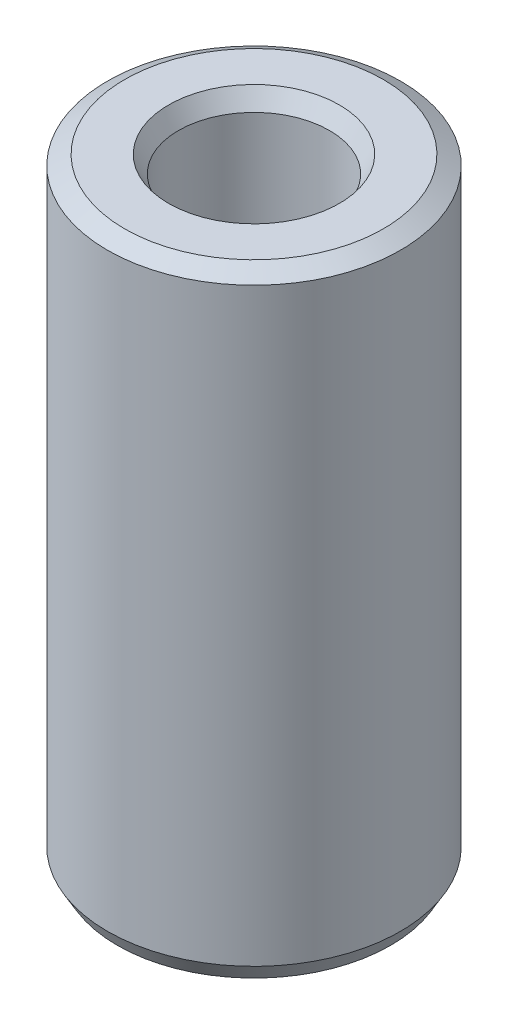
SolidWorks part; units mm, degrees
ref_plane "Front Plane" through (0, 0, 0) normal (0, 0, 1) x (1, 0, 0)
ref_plane "Top Plane" through (0, 0, 0) normal (0, 1, 0) x (1, 0, 0)
ref_plane "Right Plane" through (0, 0, 0) normal (1, 0, 0) x (0, 0, -1)
sketch "Sketch1" plane through (0, 0, 0) normal (0, 1, 0) x (1, 0, 0)
  circle A0 centre (0, 0) radius 52.5
  dimension "SLEEVE_OD" = 105
extrude "Boss-Extrude1" add sketch "Sketch1" along normal blind 221.0291
sketch "Sketch2" plane through (0, 0, 0) normal (0, 1, 0) x (1, 0, 0)
  circle A0 centre (0, 0) radius 27.0375
  dimension "BORE_D" = 54.0749
extrude "Cut-Extrude1" cut sketch "Sketch2" along normal through all
chamfer "Chamfer1" distance 3.5514 angle 60 4 edges at (0, 221.0291, 27.0375) (0, 0, 27.0375) (0, 0, 52.5) (0, 221.0291, 52.5) first distance on face at (0, 221.0291, 27.0375) first distance on face at (0, 0, 27.0375) first distance on face at (0, 221.0291, 52.5)
